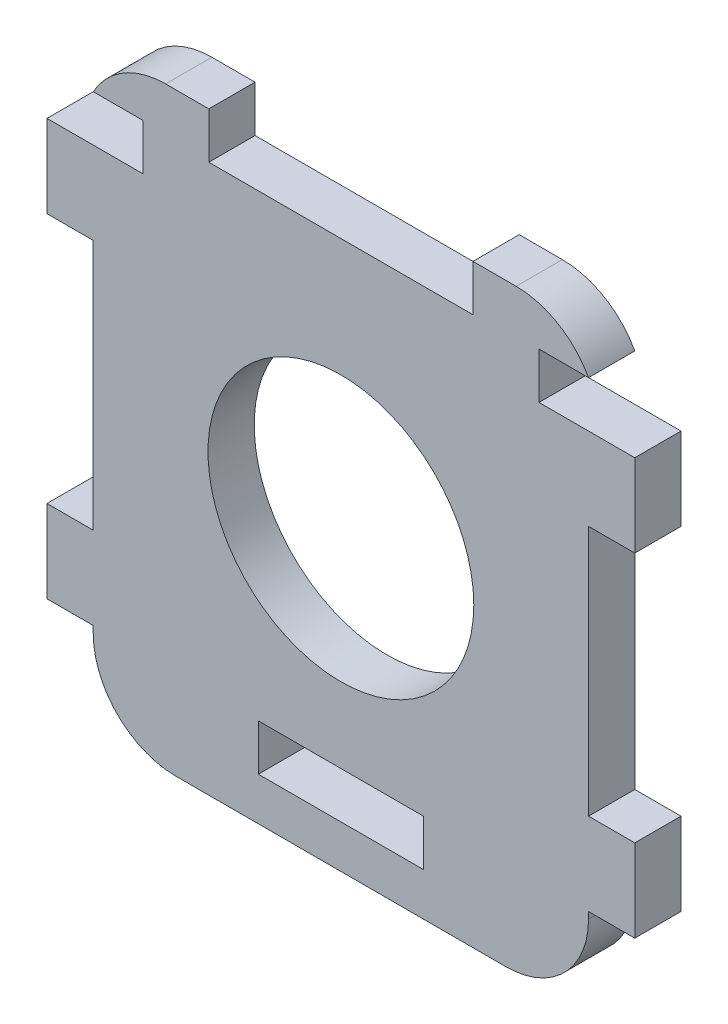
SolidWorks part; units mm, degrees
material "Фанера"
ref_plane "Front Plane" through (0, 0, 0) normal (0, 0, 1) x (1, 0, 0)
ref_plane "Top Plane" through (0, 0, 0) normal (0, 1, 0) x (1, 0, 0)
ref_plane "Right Plane" through (0, 0, 0) normal (1, 0, 0) x (0, 0, -1)
sketch "Эскиз1" plane through (0, 0, 0) normal (0, 0, 1) x (1, 0, 0)
  line L0 (-15, 12.6) -> (-17.8, 12.6)
  line L1 (-15, -18) -> (15, -18)
  line L2 (-15, -18) -> (-15, -12.6)
  line L3 (-15, 18) -> (-8, 18)
  line L4 (15, -18) -> (15, -12.6)
  line L5 (-15, -18) -> (15, 18) construction
  line L6 (-15, 18) -> (15, -18) construction
  line L7 (-17.8, 12.6) -> (-17.8, 7.6)
  line L8 (-17.8, 7.6) -> (-15, 7.6)
  line L9 (-24.8552, 0) -> (28.9627, 0) construction
  line L10 (0, 23.0741) -> (0, -18.911) construction
  line L11 (-15, 15.4) -> (-15, 18)
  line L12 (17.8, 7.6) -> (15, 7.6)
  line L13 (17.8, 12.6) -> (17.8, 7.6)
  line L14 (15, 12.6) -> (17.8, 12.6)
  line L15 (15, 15.4) -> (15, 18)
  line L16 (15, -12.6) -> (17.8, -12.6)
  line L17 (17.8, -12.6) -> (17.8, -7.6)
  line L18 (17.8, -7.6) -> (15, -7.6)
  line L19 (-17.8, -7.6) -> (-15, -7.6)
  line L20 (-17.8, -12.6) -> (-17.8, -7.6)
  line L21 (-15, -12.6) -> (-17.8, -12.6)
  line L22 (-15, -7.6) -> (-15, 7.6)
  line L23 (15, -7.6) -> (15, 7.6)
  line L24 (5, -15.4) -> (-5, -15.4)
  line L31 (-5, -12.6) -> (-5, -15.4)
  line L32 (5, -12.6) -> (-5, -12.6)
  line L33 (5, -12.6) -> (5, -15.4)
  line L37 (15, 15.4) -> (12, 15.4)
  line L42 (8, 18) -> (15, 18)
  line L43 (-8, 15.2) -> (8, 15.2)
  line L44 (-8, 15.2) -> (-8, 18)
  line L46 (8, 15.2) -> (8, 18)
  line L47 (-8, 15.2) -> (0, 18) construction
  line L48 (0, 18) -> (8, 15.2) construction
  line L56 (-15, 12.6) -> (-12, 12.6)
  line L58 (-15, 15.4) -> (-12, 15.4)
  line L59 (-12, 12.6) -> (-12, 15.4)
  line L60 (-15, 12.6) -> (-12, 15.4) construction
  line L61 (-15, 15.4) -> (-12, 12.6) construction
  line L62 (12, 12.6) -> (12, 15.4)
  line L63 (15, 12.6) -> (12, 12.6)
  circle A0 centre (0, 0) radius 8.05
  point P0 (0, 0)
  point P28 (0, 14)
  point P29 (-13.5, 14)
  point P38 (-12.4083, 14.2437)
  point P42 (0, 18)
  dimension "D2" = 16.1
  dimension "D1" = 30
  dimension "D3" = 36
  dimension "D4" = 5
  dimension "D5" = 2.8
  dimension "D6" = 5.4
  dimension "D7" = 3
  dimension "D8" = 2.8
  dimension "D10" = 2.8
  dimension "D11" = 16
  dimension "D12" = 8
extrude "Бобышка-Вытянуть1" add sketch "Эскиз1" along normal mid plane 2.8
fillet "Скругление1" radius 5 4 edges at (-15, 18, 0) (15, -18, 0) (-15, -18, 0) (15, 18, 0)
